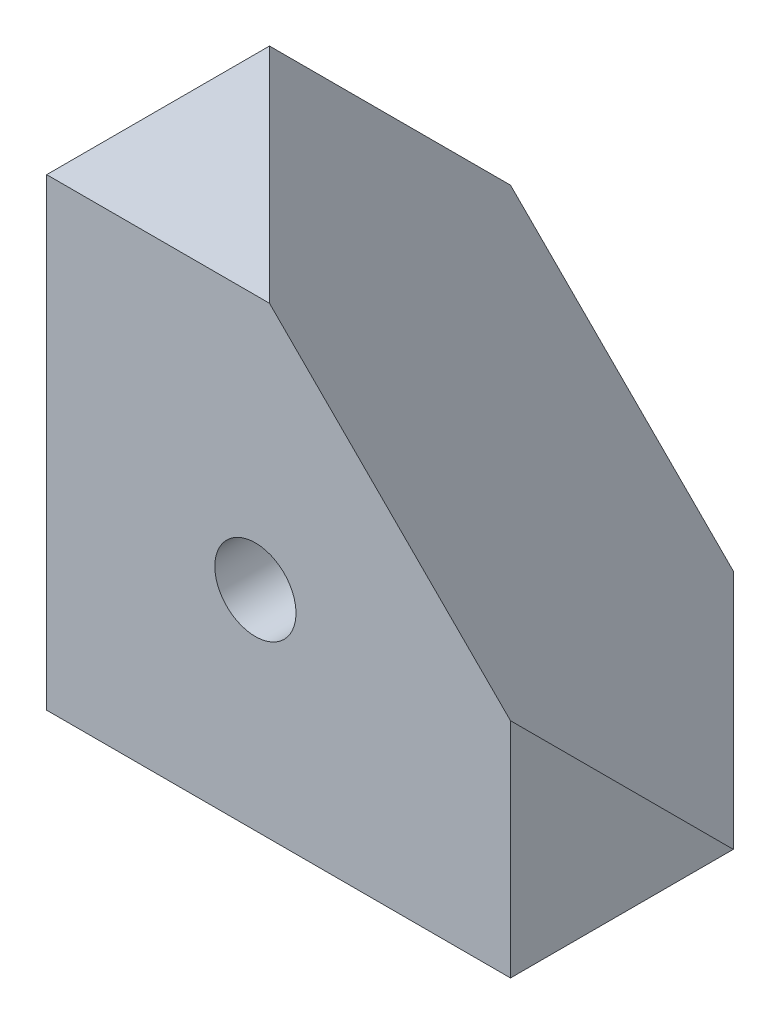
SolidWorks part; units mm, degrees
ref_plane "Plan de face" through (0, 0, 0) normal (0, 0, 1) x (1, 0, 0)
ref_plane "Plan de dessus" through (0, 0, 0) normal (0, 1, 0) x (1, 0, 0)
ref_plane "Plan de droite" through (0, 0, 0) normal (1, 0, 0) x (0, 0, -1)
sketch "Esquisse1" plane through (0, 0, 0) normal (0, 0, 1) x (1, 0, 0)
  line L1 (0, 0) -> (20, 0)
  line L2 (0, 0) -> (0, 20)
  line L3 (0, 20) -> (20, 20)
  line L4 (20, 0) -> (20, 20)
  dimension "D1" = 20
  dimension "D2" = 20
extrude "Boss.-Extru.1" add sketch "Esquisse1" along normal blind 20
ref_plane "Plan1" through (6.6667, 6.6667, -6.6667) normal (-0.5774, -0.5774, 0.5774) x (0.8165, -0.4082, 0.4082)
sketch "Esquisse2" plane through (6.6667, 6.6667, -6.6667) normal (-0.5774, -0.5774, 0.5774) x (0.8165, -0.4082, 0.4082)
  line L0 (24.4949, 14.1421) -> (16.3299, 28.2843) construction
  line L1 (-8.165, 14.1421) -> (24.4949, 14.1421) construction
  line L2 (-8.165, 28.2843) -> (-8.165, 0)
  line L3 (-8.165, 0) -> (24.4949, 0)
  line L4 (24.4949, 28.2843) -> (24.4949, 0)
  line L5 (0, 0) -> (16.3299, 0) construction
  line L6 (-8.165, 28.2843) -> (24.4949, 28.2843)
  point P5 (22.0454, 12.7279)
  point P8 (22.0454, -1.8866)
extrude "Enlèv. mat.-Extru.1" cut sketch "Esquisse2" against normal through all and the other way blind 6
sketch "Esquisse4" plane through (0, 0, 0) normal (0, -1, 0) x (1, 0, 0)
  line L0 (0, 20) -> (20, 20) construction
  line L1 (0, 20) -> (0, 0) construction
  circle A0 centre (9, 11) radius 1.75
  dimension "D1" = 9
  dimension "D2" = 9
  dimension "D3" = 3.5
extrude "Enlèv. mat.-Extru.2" cut sketch "Esquisse4" against normal blind 8 and the other way through all
sketch "Esquisse5" plane through (0, 0, 20) normal (0, 0, 1) x (1, 0, 0)
  line L0 (0, 0) -> (20, 0) construction
  line L1 (0, 20) -> (0, 0) construction
  circle A0 centre (9, 9) radius 1.75
  dimension "D1" = 3.5
  dimension "D2" = 9
  dimension "D3" = 9
extrude "Enlèv. mat.-Extru.3" cut sketch "Esquisse5" against normal blind 8 and the other way through all
sketch "Esquisse6" plane through (0, 0, 0) normal (-1, 0, 0) x (0, 0, 1)
  line L0 (20, 20) -> (20, 0) construction
  line L1 (20, 0) -> (0, 0) construction
  circle A0 centre (11, 9) radius 1.75
  dimension "D1" = 3.5
  dimension "D2" = 9
  dimension "D3" = 9
extrude "Enlèv. mat.-Extru.4" cut sketch "Esquisse6" against normal blind 8 and the other way through all
